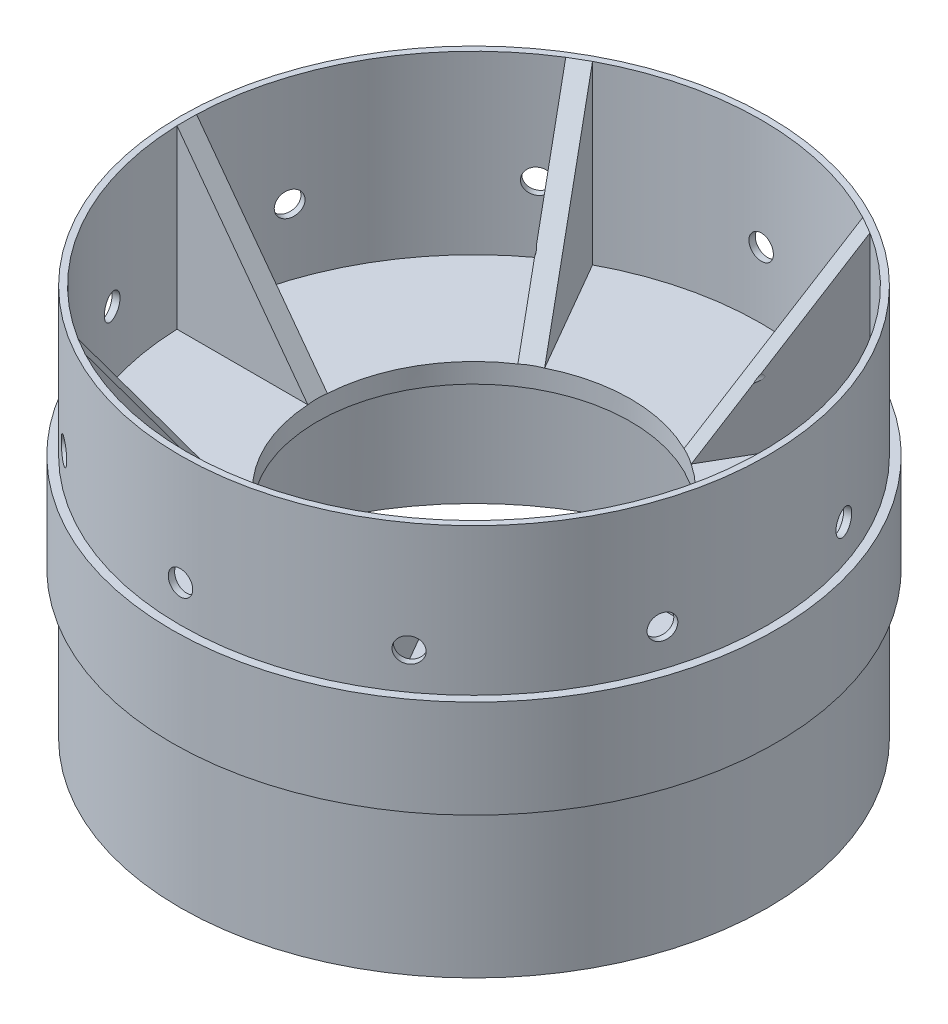
SolidWorks part; units mm, degrees
material "2024-T4"
ref_plane "Front Plane" through (0, 0, 0) normal (0, 0, 1) x (1, 0, 0)
ref_plane "Top Plane" through (0, 0, 0) normal (0, 1, 0) x (1, 0, 0)
ref_plane "Right Plane" through (0, 0, 0) normal (1, 0, 0) x (0, 0, -1)
sketch "Sketch1" plane through (0, 0, 0) normal (0, 1, 0) x (1, 0, 0)
  circle A0 centre (0, 0) radius 74.549
  circle A1 centre (0, 0) radius 78.359
  dimension "D1" = 149.098
  dimension "D2" = 156.718
extrude "Boss-Extrude1" add sketch "Sketch1" along normal blind 25.4
sketch "Sketch2" plane through (0, 25.4, 0) normal (0, 1, 0) x (1, 0, 0)
  circle A0 centre (0, 0) radius 76.2
  circle A1 centre (0, 0) radius 74.549
extrude "Boss-Extrude2" add sketch "Sketch2" along normal blind 38.1
sketch "Sketch3" plane through (0, 0, 0) normal (0, -1, 0) x (1, 0, 0)
  circle A0 centre (0, 0) radius 76.2
  circle A1 centre (0, 0) radius 74.549
  dimension "D1" = 152.4
extrude "Boss-Extrude3" add sketch "Sketch3" along normal blind 38.1
ref_plane "Plane1" through (0, 12.7, 0) normal (0, 1, 0) x (1, 0, 0)
sketch "Sketch4" plane through (0, 12.7, 0) normal (0, 1, 0) x (1, 0, 0)
  circle A0 centre (0, 0) radius 74.549
  circle A1 centre (0, 0) radius 40.64
  dimension "D1" = 81.28
extrude "Boss-Extrude4" add sketch "Sketch4" along normal blind 5.08
sketch "Sketch5" plane through (0, 17.78, 0) normal (0, 1, 0) x (1, 0, 0)
  line L0 (40.5605, 2.54) -> (74.5057, 2.54)
  line L2 (74.5057, -2.54) -> (40.5605, -2.54)
  line L3 (34.8136, 0) -> (44.1618, 0) construction
  line L19 (22.48, -33.8565) -> (39.4526, -63.2538)
  line L20 (35.0532, -65.7938) -> (18.0806, -36.3965)
  line L21 (-18.0806, -36.3965) -> (-35.0532, -65.7938)
  line L22 (-39.4526, -63.2538) -> (-22.48, -33.8565)
  line L29 (-40.5605, -2.54) -> (-74.5057, -2.54)
  line L30 (-74.5057, 2.54) -> (-40.5605, 2.54)
  line L31 (-22.48, 33.8565) -> (-39.4526, 63.2538)
  line L32 (-35.0532, 65.7938) -> (-18.0806, 36.3965)
  line L33 (18.0806, 36.3965) -> (35.0532, 65.7938)
  line L34 (39.4526, 63.2538) -> (22.48, 33.8565)
  circle A0 centre (0, 0) radius 40.64 construction
  arc A1 (39.4526, -63.2538) -> (35.0532, -65.7938) centre (0, 0) cw
  arc A2 (74.5057, 2.54) -> (74.5057, -2.54) centre (0, 0) cw
  circle A3 centre (0, 0) radius 74.549 construction
  arc A4 (40.5605, 2.54) -> (40.5605, -2.54) centre (0, 0) cw
  arc A19 (22.48, -33.8565) -> (18.0806, -36.3965) centre (0, 0) cw
  arc A20 (-35.0532, -65.7938) -> (-39.4526, -63.2538) centre (0, 0) cw
  arc A21 (-18.0806, -36.3965) -> (-22.48, -33.8565) centre (0, 0) cw
  arc A28 (-74.5057, -2.54) -> (-74.5057, 2.54) centre (0, 0) cw
  arc A29 (-40.5605, -2.54) -> (-40.5605, 2.54) centre (0, 0) cw
  arc A30 (-39.4526, 63.2538) -> (-35.0532, 65.7938) centre (0, 0) cw
  arc A31 (-22.48, 33.8565) -> (-18.0806, 36.3965) centre (0, 0) cw
  arc A32 (35.0532, 65.7938) -> (39.4526, 63.2538) centre (0, 0) cw
  arc A33 (18.0806, 36.3965) -> (22.48, 33.8565) centre (0, 0) cw
  point P34 (0, 0)
  point P40 (0, 0)
  dimension "D4" = 0
  dimension "D1" = 2.54
  dimension "D2" = 2.54
  dimension "D3" = 6
extrude "Boss-Extrude10" add sketch "Sketch5" along normal blind 45.72
sketch "Sketch6" plane through (0, 0, 2.54) normal (0, 0, 1) x (1, 0, 0)
  line L0 (74.5057, 63.5) -> (40.5605, 17.78)
  line L1 (40.5605, 17.78) -> (40.5605, 63.5)
  line L2 (40.5605, 63.5) -> (74.5057, 63.5)
extrude "Cut-Extrude1" cut sketch "Sketch6" against normal blind 5.08
pattern_circular "CirPattern1" count 6 over 360 about axis through (0, 12.7, 0) along (0, 1, 0) of "Cut-Extrude1"
sketch "Sketch7" plane through (0, 0, 0) normal (0, 0, 1) x (1, 0, 0)
  line L0 (0, 42.3302) -> (0, 74.728) construction
  line L1 (78.359, 25.4) -> (-78.359, 25.4) construction
  circle A0 centre (0, 34.925) radius 3.175
  dimension "D1" = 6.35
  dimension "D2" = 9.525
extrude "Cut-Extrude2" cut sketch "Sketch7" against normal through all
ref_axis "Axis1" through (0, 42.3302, 0) along (0, 1, 0)
pattern_circular "CirPattern2" count 10 over 360 about axis through (0, 42.3302, 0) along (0, 1, 0) of "Cut-Extrude2"
